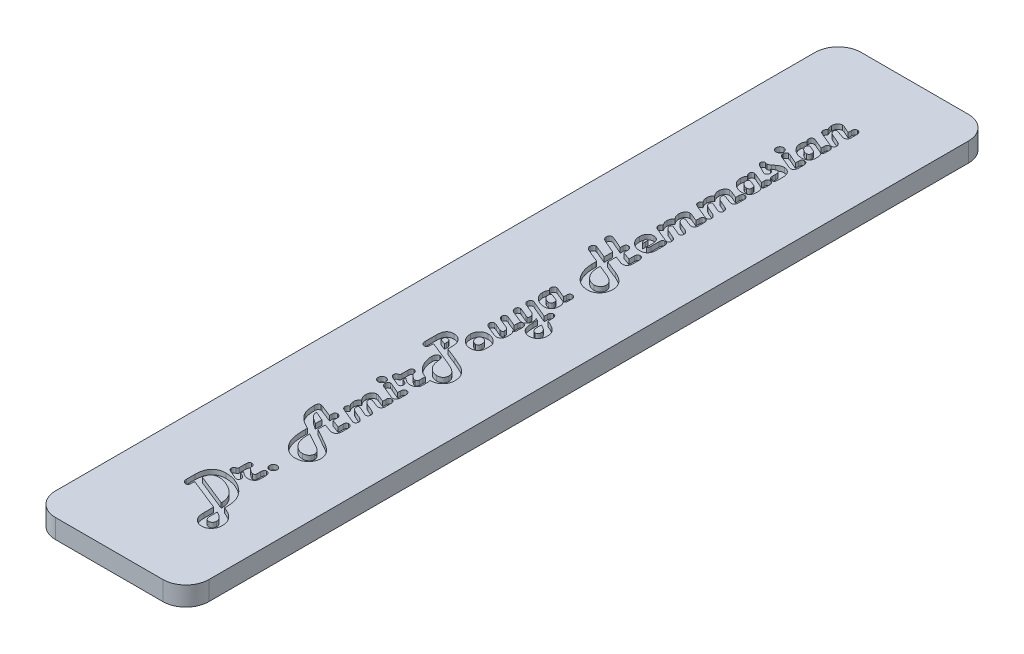
SolidWorks part; units mm, degrees
ref_plane "Front Plane" through (0, 0, 0) normal (0, 0, 1) x (1, 0, 0)
ref_plane "Top Plane" through (0, 0, 0) normal (0, 1, 0) x (1, 0, 0)
ref_plane "Right Plane" through (0, 0, 0) normal (1, 0, 0) x (0, 0, -1)
sketch "Sketch1" plane through (0, 0, 0) normal (0, 0, 1) x (1, 0, 0)
  line L0 (0, 1.5875) -> (0, -1.5875)
  line L1 (-12.7, 0) -> (12.7, 0) construction
  point P6 (0, 0)
  dimension "Width" = 25.4
  dimension "Thk" = 3.175
sketch "Sketch2" plane through (0, 0, 0) normal (1, 0, 0) x (0, 0, -1)
  line L0 (66.675, 0) -> (-66.675, 0)
  point P4 (0, 0)
  dimension "Length" = 133.35
sketch "Sketch3" plane through (0, 0, 0) normal (0, 0, 1) x (1, 0, 0)
  line L1 (12.7, 1.5875) -> (-12.7, 1.5875)
  line L2 (12.7, 1.5875) -> (12.7, -1.5875)
  line L3 (12.7, -1.5875) -> (-12.7, -1.5875)
  line L4 (-12.7, 1.5875) -> (-12.7, -1.5875)
  line L5 (12.7, 1.5875) -> (-12.7, -1.5875) construction
  line L6 (12.7, -1.5875) -> (-12.7, 1.5875) construction
  point P0 (0, 0)
extrude "Boss-Extrude1" add sketch "Sketch3" along normal up to vertex (66.675 mm away) and the other way up to vertex (66.675 mm away) up to point (0, 0, 66.675) other way up to point (0, 0, -66.675)
sketch "Sketch5" plane through (0, 1.5875, 0) normal (0, 1, 0) x (1, 0, 0)
  line L2 (9.652, -66.675) -> (-9.398, -66.675) construction
  line L3 (-12.7, -63.5025) -> (-12.7, 63.627) construction
  line L12 (12.7, -66.675) -> (12.7, 66.675)
  line L13 (12.7, 66.675) -> (-12.7, 66.675)
  line L14 (-12.7, 66.675) -> (-12.7, -66.675)
  line L15 (-12.7, -66.675) -> (12.7, -66.675)
  line L16 (12.7, -62.865) -> (12.7, 62.865)
  line L17 (8.89, 66.675) -> (-8.89, 66.675)
  line L18 (-12.7, 62.865) -> (-12.7, -62.865)
  line L19 (-8.89, -66.675) -> (8.89, -66.675)
  arc A8 (12.7, 62.865) -> (8.89, 66.675) centre (8.89, 62.865) ccw
  arc A9 (-8.89, 66.675) -> (-12.7, 62.865) centre (-8.89, 62.865) ccw
  arc A10 (12.7, -62.865) -> (8.89, -66.675) centre (8.89, -62.865) cw
  arc A11 (-8.89, -66.675) -> (-12.7, -62.865) centre (-8.89, -62.865) cw
  dimension "D2" = 3.81
  dimension "D1" = 0
extrude "Cut-Extrude2" cut sketch "Sketch5" against normal through all flip side to cut
sketch "Sketch4" plane through (0, 1.5875, 0) normal (0, 1, 0) x (1, 0, 0)
  line L0 (0, 0) -> (2.54, 0) construction
  line L1 (2.54, -66.675) -> (2.54, 66.675) construction
  line L2 (8.89, 66.675) -> (-8.89, 66.675) construction
  text T0 "Dr. AmirPouya Hemmasian" font "Harlow Solid Italic" height in points 24
  point P8 (2.54, 0)
  dimension "D1" = 2.54
extrude "Cut-Extrude1" cut sketch "Sketch4" against normal blind 0.7937
